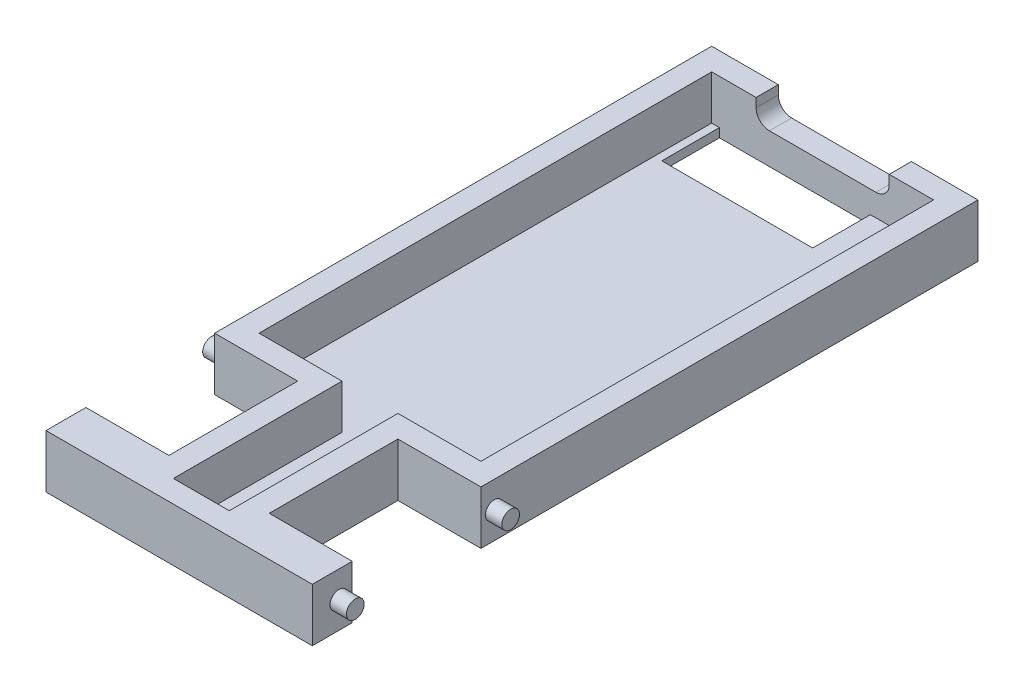
SolidWorks part; units mm, degrees
note: The reader was unsure of these and kept them because the rebuilt part matched: shared geometry of "Sketch1<2>", "Sketch2<3>".
ref_plane "Front Plane" through (0, 0, 0) normal (0, 0, 1) x (1, 0, 0)
ref_plane "Top Plane" through (0, 0, 0) normal (0, 1, 0) x (1, 0, 0)
ref_plane "Right Plane" through (0, 0, 0) normal (1, 0, 0) x (0, 0, -1)
sketch "Sketch1" plane through (0, 0, 0) normal (0, 1, 0) x (1, 0, 0)
  line L1 (0, 0) -> (60, 0)
  line L2 (0, 0) -> (0, -150)
  line L3 (0, -150) -> (60, -150)
  line L4 (60, 0) -> (60, -150)
  line L5 (5, -5) -> (55, -5)
  line L6 (5, -5) -> (5, -145)
  line L7 (5, -145) -> (55, -145)
  line L8 (55, -5) -> (55, -145)
  line L9 (36.25, -45.8678) -> (23.75, -45.8678)
  line L10 (36.25, -45.8678) -> (36.25, -23.3678)
  line L11 (36.25, -23.3678) -> (23.75, -23.3678)
  line L12 (23.75, -45.8678) -> (23.75, -23.3678)
  point P9 (30, -5)
  point P10 (30, 0)
  point P11 (5, -75)
  point P12 (0, -75)
  point P17 (30, -23.3678)
  dimension "D1" = 60
  dimension "D2" = 150
  dimension "D3" = 5
  dimension "D4" = 5
  dimension "D5" = 22.5
  dimension "D6" = 12.5
extrude "Boss-Extrude1" add sketch "Sketch1" along normal blind 10 contours L4 L1 L2 L3 L5 L8 L7 L6
extrude "Boss-Extrude2" add sketch "Sketch1<2>" against normal blind 2 contours L8 L5 L6 L7 | L4 L1 L2 L3 L5 L8 L7 L6 | L12 L9 L10 L11
sketch "Sketch1<2>" plane through (0, 0, 0) normal (0, 1, 0) x (1, 0, 0) same geometry as "Sketch1"
sketch "Sketch2" plane through (0, 0, 0) normal (-1, 0, 0) x (0, 0, 1)
  line L1 (144, 4) -> (109, 4) construction
  line L2 (150, 10) -> (150, -2) construction
  line L4 (141, -2) -> (112, -2)
  line L5 (141, -2) -> (141, 10)
  line L6 (141, 10) -> (112, 10)
  line L7 (112, -2) -> (112, 10)
  line L8 (0, -2) -> (150, -2) construction
  line L9 (0, 10) -> (150, 10) construction
  circle A2 centre (144, 4) radius 2
  circle A3 centre (109, 4) radius 2
  circle A4 centre (126.5, 4) radius 14.5 construction
  point P11 (150, 4)
  dimension "D1" = 29
  dimension "D2" = 4
  dimension "D3" = 35
  dimension "D4" = 6
extrude "Cut-Extrude1" cut sketch "Sketch2" against normal blind 18.7 contours L5 L4 L7 L6
extrude "Boss-Extrude3" add sketch "Sketch2<3>" along normal blind 3.7 contours A3 | A2
sketch "Sketch2<3>" plane through (0, 0, 0) normal (-1, 0, 0) x (0, 0, 1) same geometry as "Sketch2"
ref_plane "Plane1" through (30, 0, 0) normal (-1, 0, 0) x (0, 0, 1)
mirror "Mirror1" about plane through (30, 0, 0) normal (-1, 0, 0) of "Boss-Extrude3", "Cut-Extrude1"
sketch "Sketch3" plane through (0, 0, 0) normal (0, 1, 0) x (1, 0, 0)
  line L0 (0, -107) -> (23.7, -107)
  line L1 (23.7, -107) -> (23.7, -146)
  line L2 (23.7, -146) -> (0, -146)
  line L3 (60, -146) -> (36.3, -146)
  line L4 (36.3, -146) -> (36.3, -107)
  line L5 (36.3, -107) -> (60, -107)
  line L12 (60, -112) -> (60, 0)
  line L17 (0, -150) -> (60, -150)
  line L18 (0, -141) -> (0, -150)
  line L19 (18.7, -141) -> (0, -141)
  line L20 (18.7, -112) -> (18.7, -141)
  line L21 (0, -112) -> (18.7, -112)
  line L22 (0, 0) -> (0, -112)
  line L23 (60, 0) -> (0, 0)
  line L24 (60, -112) -> (60, 0)
  line L29 (0, -150) -> (60, -150)
  line L30 (0, -141) -> (0, -150)
  line L31 (18.7, -141) -> (0, -141)
  line L32 (18.7, -112) -> (18.7, -141)
  line L33 (0, -112) -> (18.7, -112)
  line L34 (0, 0) -> (0, -112)
  line L35 (60, 0) -> (0, 0)
  line L38 (41.3, -112) -> (60, -112)
  line L39 (41.3, -112) -> (60, -112)
  line L40 (41.3, -141) -> (41.3, -112)
  line L41 (41.3, -141) -> (41.3, -112)
  line L42 (60, -141) -> (41.3, -141)
  line L43 (60, -141) -> (41.3, -141)
  line L44 (60, -150) -> (60, -141)
  line L45 (60, -150) -> (60, -141)
  dimension "D1" = 0
  dimension "D2" = 5
  dimension "D3" = 5
extrude "Boss-Extrude4" add sketch "Sketch3" along normal up to surface (10 mm away) up to face at (30, 10, 57.25)
sketch "Sketch4" plane through (0, -2, 0) normal (0, -1, 0) x (1, 0, 0)
  line L1 (6.75, 5) -> (40.75, 5)
  line L2 (6.75, 5) -> (6.75, 18)
  line L3 (6.75, 18) -> (40.75, 18)
  line L4 (40.75, 5) -> (40.75, 18)
  line L5 (30, 6.6) -> (30, -6.6) construction
  line L6 (5, 5) -> (55, 5) construction
  dimension "D1" = 34
  dimension "D2" = 10.75
  dimension "D3" = 13
extrude "Cut-Extrude2" cut sketch "Sketch4" against normal through all both and the other way through all
sketch "Sketch5" plane through (0, 0, 0) normal (0, 0, -1) x (-1, 0, 0)
  line L0 (0, 10) -> (-60, 10) construction
  line L1 (-45, 10) -> (-15, 10)
  line L2 (-45, 10) -> (-45, 5)
  line L3 (-45, 5) -> (-15, 5)
  line L4 (-15, 10) -> (-15, 5)
  line L6 (-30, -6.6) -> (-30, 6.6) construction
  point P6 (-30, 10)
  dimension "D1" = 5
  dimension "D2" = 30
extrude "Cut-Extrude3" cut sketch "Sketch5" against normal up to next
fillet "Fillet1" radius 3 2 edges at (15, 5, 2.5) (45, 5, 2.5)
